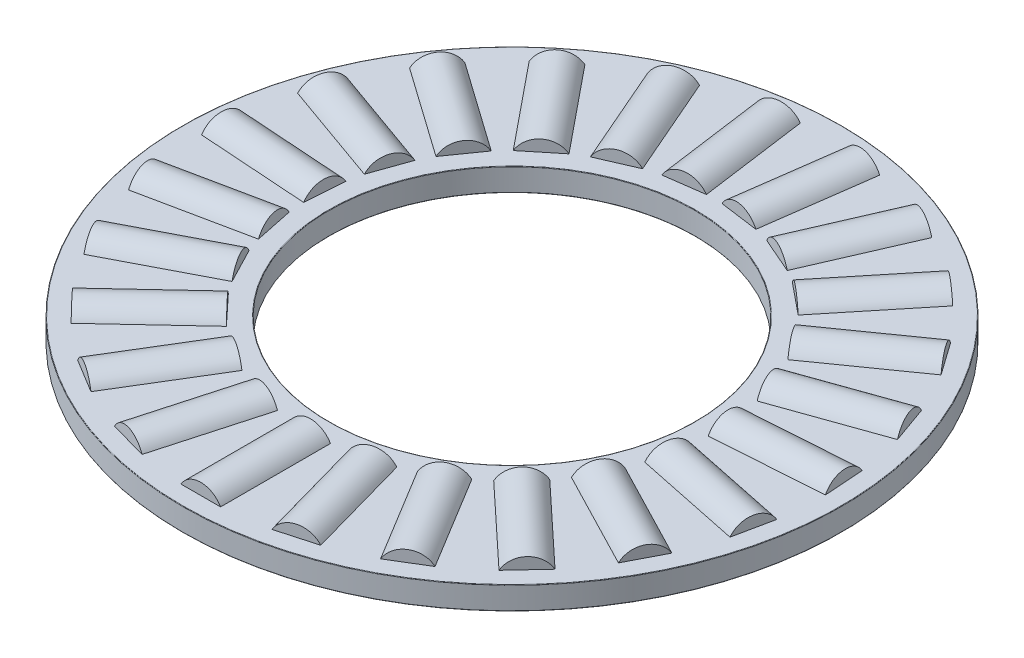
SolidWorks part; units mm, degrees
ref_plane "Front Plane" through (0, 0, 0) normal (0, 0, 1) x (1, 0, 0)
ref_plane "Top Plane" through (0, 0, 0) normal (0, 1, 0) x (1, 0, 0)
ref_plane "Right Plane" through (0, 0, 0) normal (1, 0, 0) x (0, 0, -1)
sketch "Sketch1" plane through (0, 0, 0) normal (1, 0, 0) x (0, 0, -1)
  line L0 (-14.2875, 0) -> (14.2875, 0) construction
  line L1 (0, -0.9922) -> (0, 0.9922) construction
  line L2 (-14.2875, 0.4961) -> (-7.9375, 0.4961)
  line L3 (-14.2875, 0.4961) -> (-14.2875, -0.4961)
  line L4 (-14.2875, -0.4961) -> (-7.9375, -0.4961)
  line L5 (-7.9375, 0.4961) -> (-7.9375, -0.4961)
  line L7 (-11.1125, 0.9922) -> (-11.1125, 0.4961) construction
  line L8 (-13.4938, 0.9922) -> (-8.7312, 0.9922) construction
  line L9 (-13.4938, 0.9922) -> (-13.4938, -0.9922) construction
  line L10 (-13.4938, -0.9922) -> (-8.7312, -0.9922) construction
  line L11 (-8.7312, 0.9922) -> (-8.7312, -0.9922) construction
  point P16 (-13.4938, 0)
  dimension "D1" = 4.7625
  dimension "OD" = 28.575
  dimension "Shaft Dia" = 15.875
  dimension "Th" = 1.9844
  dimension "D2" = 0.9922
  dimension "D3" = 6.35
revolve "Revolve1" add sketch "Sketch1" angle 360 about L1
sketch "Sketch3" plane through (0, 0, 0) normal (1, 0, 0) x (0, 0, -1)
  line L0 (-13.4938, 0.9922) -> (-13.4938, -0.9922) construction
  line L1 (-13.4938, 0) -> (-8.7312, 0)
  line L2 (-13.4938, 0) -> (-13.4938, 0.9922)
  line L3 (-13.4938, 0.9922) -> (-8.7312, 0.9922)
  line L4 (-8.7312, 0) -> (-8.7312, 0.9922)
revolve "Cut-Revolve1" cut sketch "Sketch3" angle 360 about L1
sketch "Sketch2" plane through (0, 0, 0) normal (1, 0, 0) x (0, 0, -1)
  line L1 (-13.4938, 0) -> (-8.7312, 0)
  line L2 (-13.4938, 0) -> (-13.4938, 0.9922)
  line L3 (-13.4938, 0.9922) -> (-8.7312, 0.9922)
  line L4 (-8.7312, 0) -> (-8.7312, 0.9922)
revolve "Revolve2" add sketch "Sketch2" angle 360 about L1
ref_axis "Axis1" through (0, 0.9922, 0) along (0, -1, 0)
pattern_circular "CirPattern1" count 23 every 15.652 about axis through (0, 0.9922, 0) along (0, -1, 0) of bodies 187 411
pattern_circular "CirPattern2" count 23 every 15.652 about axis through (0, 0.9922, 0) along (0, -1, 0) of "Cut-Revolve1"
sketch "Sketch4" plane through (0, 0, 0) normal (1, 0, 0) x (0, 0, -1)
  line L0 (-14.2875, 0.4961) -> (-14.2875, -0.4961) construction
  line L1 (-14.2875, 9.1091) -> (-7.9375, 9.1091)
  line L2 (-14.2875, 9.1091) -> (-14.2875, 9.9219)
  line L3 (-14.2875, 9.9219) -> (-7.9375, 9.9219)
  line L4 (-7.9375, 9.1091) -> (-7.9375, 9.9219)
  line L5 (-14.2875, -9.9219) -> (-7.9375, -9.9219)
  line L6 (-14.2875, -9.9219) -> (-14.2875, -9.1091)
  line L7 (-14.2875, -9.1091) -> (-7.9375, -9.1091)
  line L8 (-7.9375, -9.9219) -> (-7.9375, -9.1091)
  line L10 (-7.9375, 0.4961) -> (-7.9375, -0.4961) construction
  line L11 (0, 0) -> (-14.2875, 0) construction
  line L12 (-14.2875, 0) -> (14.2875, 0) construction
  line L13 (0, -0.9922) -> (0, 0.9922) construction
  dimension "Ht" = 19.8438
  dimension "Washer Th" = 0.8128
  dimension "Washer ID" = 15.875
  dimension "Washer OD" = 28.575
revolve "Revolve3" [suppressed] add sketch "Sketch4" angle 360 about L1
fillet "Fillet1" [suppressed] radius 0.0198
fillet "Fillet2" radius 0.0198 4 edges at (0, -0.4961, -7.9375) (0, 0.4961, -7.9375) (0, -0.4961, -14.2875) (0, 0.4961, -14.2875)
fillet "Fillet3" [suppressed] radius 0.0198
equation "\"D2@Sketch1\" = \"Th@Sketch1\"*.5"
equation "\"D1@Fillet1\" = \"Th@Sketch1\"*.01"
equation "\"D1@Fillet2\" = \"D1@Fillet1\""
equation "\"D1@Fillet3\" = \"D1@Fillet1\""
equation "\"D1@Sketch1\" = \"D3@Sketch1\"*.75"
equation "\"Angle@CirPattern1\" = 360/\"Rollers@CirPattern1\""
equation "\"Rollers@CirPattern1\" = \"OD@Sketch1\"*20"
equation "\"D1@CirPattern2\" = \"Rollers@CirPattern1\""
equation "\"D2@CirPattern2\" = \"Angle@CirPattern1\""
equation "\"Ht@Sketch4\" = \"Th@Sketch1\"*10"
